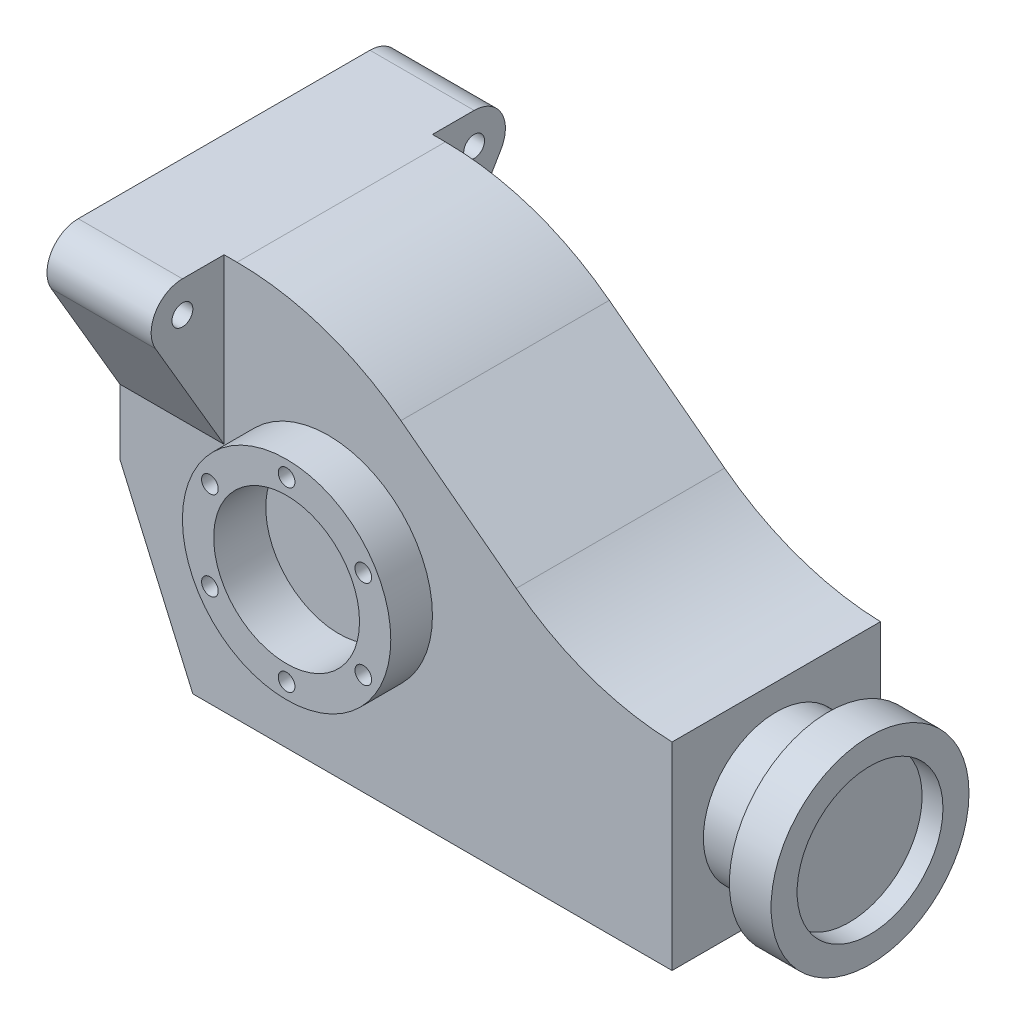
SolidWorks part; units mm, degrees
ref_plane "Płaszczyzna przednia" through (0, 0, 0) normal (0, 0, 1) x (1, 0, 0)
ref_plane "Płaszczyzna górna" through (0, 0, 0) normal (0, 1, 0) x (1, 0, 0)
ref_plane "Płaszczyzna prawa" through (0, 0, 0) normal (1, 0, 0) x (0, 0, -1)
sketch "Szkic1" plane through (0, 0, 0) normal (0, 0, 1) x (1, 0, 0)
  line L0 (-35, 190) -> (65, 190)
  line L1 (65, 190) -> (190, 95)
  line L2 (190, 95) -> (230, 95)
  line L3 (230, 95) -> (230, 0)
  line L4 (230, 0) -> (0, 0)
  line L7 (-35, 190) -> (-35, 80)
  line L8 (-35, 80) -> (0, 0)
  dimension "D1" = 265
  dimension "D2" = 190
  dimension "D3" = 95
  dimension "D4" = 80
  dimension "D5" = 230
  dimension "D6" = 100
  dimension "D7" = 40
extrude "Dodanie-wyciągnięcie1" add sketch "Szkic1" along normal mid plane 100 contours L1 L2 L3 L4 L8 L7 L0
sketch "Szkic2" plane through (230, 0, 0) normal (1, 0, 0) x (0, 0, -1)
  line L0 (-50, 95) -> (50, 0) construction
  line L1 (50, 95) -> (-50, 0) construction
  line L2 (-50, 0) -> (50, 0) construction
  circle A0 centre (0, 47.5) radius 35
  point P13 (0, 47.5)
  dimension "D1" = 70
extrude "Dodanie-wyciągnięcie2" add sketch "Szkic2" along normal blind 25 separate body
sketch "Szkic3" plane through (255, 0, 0) normal (1, 0, 0) x (0, 0, -1)
  circle A0 centre (0, 47.5) radius 47.5
  circle A1 centre (0, 47.5) radius 35 construction
  dimension "D1" = 95
extrude "Dodanie-wyciągnięcie3" add sketch "Szkic3" along normal blind 20
sketch "Szkic4" plane through (275, 0, 0) normal (1, 0, 0) x (0, 0, -1)
  circle A0 centre (0, 47.5) radius 35
  circle A1 centre (0, 47.5) radius 47.5 construction
  dimension "D1" = 70
sketch "Szkic7" plane through (0, 0, 50) normal (0, 0, 1) x (1, 0, 0)
  line L0 (-35, 190) -> (-35, 80) construction
  line L1 (-35, 190) -> (65, 190) construction
  circle A0 centre (65, 90) radius 50
  dimension "D1" = 100
  dimension "D2" = 100
  dimension "D3" = 100
extrude "Dodanie-wyciągnięcie5" add sketch "Szkic7" along normal blind 20
sketch "Szkic8" plane through (0, 0, 70) normal (0, 0, 1) x (1, 0, 0)
  circle A0 centre (65, 90) radius 35
  dimension "D1" = 70
extrude "Wytnij-wyciągnięcie1" cut sketch "Szkic8" against normal blind 25
sketch "Szkic9" plane through (0, 0, 70) normal (0, 0, 1) x (1, 0, 0)
  line L0 (65, 90) -> (65, 132.5) construction
  circle A0 centre (65, 132.5) radius 4
  circle A1 centre (101.8061, 111.25) radius 4
  circle A2 centre (65, 90) radius 35 construction
  circle A3 centre (65, 90) radius 35
  circle A4 centre (101.8061, 68.75) radius 4
  circle A5 centre (65, 47.5) radius 4
  circle A6 centre (28.1939, 68.75) radius 4
  circle A7 centre (28.1939, 111.25) radius 4
  dimension "D1" = 8
  dimension "D2" = 42.5
  dimension "D3" = 6
  dimension "D4" = 42.5
extrude "Wytnij-wyciągnięcie2" cut sketch "Szkic9" against normal blind 15 contours A0 | A1 | A4 | A5 | A6 | A7
sketch "Szkic12" plane through (-35, 0, 0) normal (-1, 0, 0) x (0, 0, 1)
  line L0 (-70, 190) -> (70, 190)
  line L1 (50, 190) -> (-50, 190) construction
  line L2 (-82.9419, 167.4166) -> (-20, 60)
  line L4 (50, 0) -> (-50, 0) construction
  line L5 (-20, 60) -> (20, 60)
  line L6 (0, 190) -> (0, 60) construction
  line L7 (82.9419, 167.4166) -> (20, 60)
  circle A0 centre (-70, 175) radius 5
  arc A1 (-70, 190) -> (-82.9419, 167.4166) centre (-70, 175) ccw
  arc A2 (70, 190) -> (82.9419, 167.4166) centre (70, 175) cw
  circle A3 centre (70, 175) radius 5
  line M4 (-50, 190) -> (-50, 80)
  line M5 (-50, 80) -> (50, 80)
  line M6 (50, 80) -> (50, 190)
  line M7 (50, 190) -> (-50, 190)
  dimension "D1" = 10
  dimension "D2" = 30
  dimension "D4" = 20
  dimension "D5" = 70
  dimension "D3" = 60
extrude "Dodanie-wyciągnięcie6" add sketch "Szkic12" against normal blind 50 contours L0 A1 L2 A0 M4 | L6 L0 L2 M4 M5 | L6 L7 M7 M5 M6 | A2 L0 L7 A3 M6 | L6 L5 L7 M5 | L6 L2 L5 M5 region at (-35, 161.1302, -63.0812) region at (-35, 137.4389, -23.9661) region at (-35, 137.4389, 23.9661) region at (-35, 161.1302, 63.0812) region at (-35, 70.7553, 13.1511) region at (-35, 70.7553, -13.1511)
mirror "Lustro1" about plane through (0, 0, 0) normal (0, 0, 1) of "Wytnij-wyciągnięcie2", "Wytnij-wyciągnięcie1", "Dodanie-wyciągnięcie5"
fillet "Zaokrąglenie2" radius 130 1 edges at (65, 190, 0)
fillet "Zaokrąglenie3" radius 130 1 edges at (190, 95, 0)
extrude "Wytnij-wyciągnięcie3" cut sketch "Szkic4" against normal blind 10
